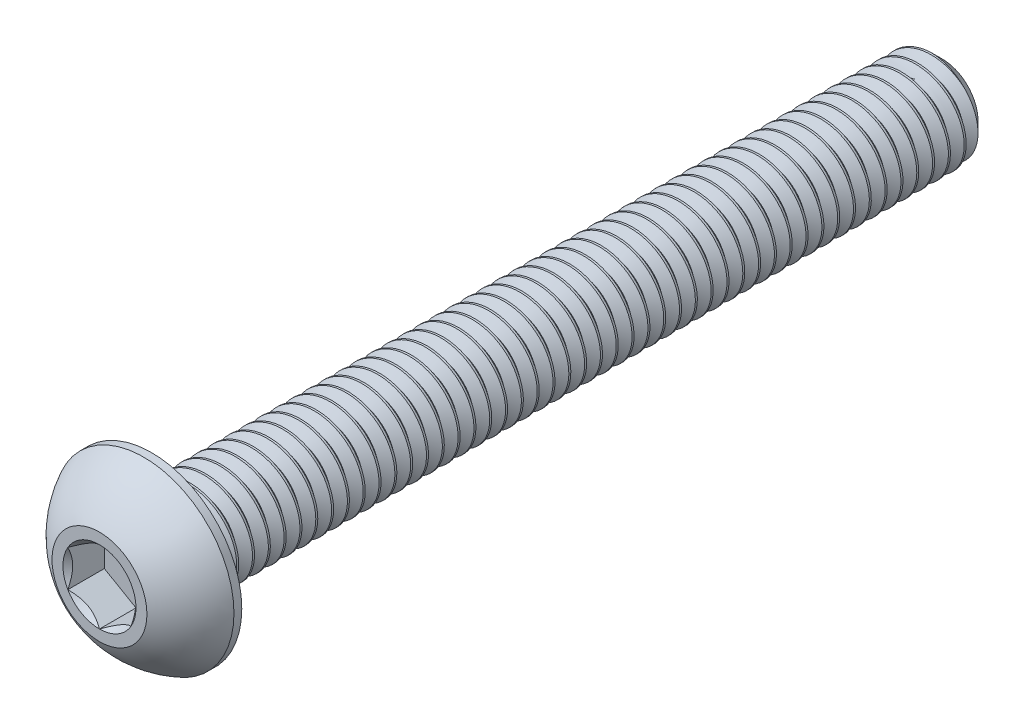
SolidWorks part; units mm, degrees
note: '?' marks a value the reader was unsure of.
ref_plane "Front" through (0, 0, 0) normal (0, 0, 1) x (1, 0, 0)
ref_plane "Top" through (0, 0, 0) normal (0, 1, 0) x (1, 0, 0)
ref_plane "Right" through (0, 0, 0) normal (1, 0, 0) x (0, 0, -1)
sketch "Sketch1" plane through (0, 0, 0) normal (1, 0, 0) x (0, 0, -1)
  line L2 (1.65, 1.5) -> (26.65, 1.5)
  line L3 (26.65, 1.5) -> (26.65, 0)
  line L4 (26.65, 0) -> (1.65, 0)
  line L6 (1.4025, 2.85) -> (1.65, 2.85) construction
  line L7 (26.65, 1.5) -> (26.65, -1.5) construction
  line L8 (0, 0) -> (1.65, 0) construction
  line L9 (1.65, 2.85) -> (1.65, -2.85) construction
  line L11 (1.65, 1.5) -> (1.65, 0)
  line L13 (0, 1) -> (0, -1) construction
  line L14 (0, 1) -> (0, 1.5) construction
  arc A3 (0, 1.5) -> (1.4025, 2.85) centre (2.7948, 0) cw construction
  dimension "D1" = 0.2475
revolve "Revolve1" add sketch "Sketch1" angle 360 mid plane about L4
sketch "Sketch3" plane through (0, 0, -26.65) normal (0, 0, -1) x (-1, 0, 0)
  circle A0 centre (0, 0) radius 1.5
curve "Helix/Spiral1" pitch 0.5 height 25.5 turns 51
chamfer "Chamfer1" distance 0.375 angle 45 1 edges at (0, 1.5, -26.65)
sketch "Sketch7" plane through (0, 0, 0) normal (1, 0, 0) x (0, 0, -1)
  line L6 (1.4025, 2.85) -> (1.65, 2.85) construction
  line L8 (0, 0) -> (1.65, 0) construction
  line L11 (1.65, 2.85) -> (1.65, -2.85) construction
  line L12 (1.4025, 2.85) -> (1.65, 2.85)
  line L13 (0, 0) -> (1.65, 0)
  line L14 (0, 1) -> (0, -1) construction
  line L15 (1.65, 2.85) -> (1.65, 0)
  line L16 (0, 1.5) -> (0, 0)
  arc A2 (1.4025, 2.85) -> (0, 1.5) centre (2.7948, 0) ccw construction
  arc A3 (1.4025, 2.85) -> (0, 1.5) centre (2.7948, 0) ccw
revolve "Revolve2" add sketch "Sketch7" angle 360 mid plane about L13
sketch "Sketch5" plane through (0, 0, 0) normal (0, 0, 1) x (1, 0, 0)
  line L1 (1, -0.5774) -> (1, 0.5774)
  line L2 (1, 0.5774) -> (0, 1.1547)
  line L3 (0, 1.1547) -> (-1, 0.5774)
  line L4 (-1, 0.5774) -> (-1, -0.5774)
  line L5 (-1, -0.5774) -> (0, -1.1547)
  line L6 (0, -1.1547) -> (1, -0.5774)
  circle A0 centre (0, 0) radius 1 construction
extrude "Cut-Extrude2" cut sketch "Sketch5" against normal blind 1.155
sketch "Sketch6" plane through (0, 0, 0) normal (0, 0, 1) x (1, 0, 0)
  circle A0 centre (0, 0) radius 1.1547
extrude "Cut-Extrude3" cut sketch "Sketch6" against normal blind 1.155 draft 45
sketch "Sketch2" plane through (0, 0, 0) normal (1, 0, 0) x (0, 0, -1)
  line L0 (26.275, 1.5) -> (26.7125, 1.5)
  line L1 (26.7125, 1.5) -> (26.525, 1.1752)
  line L2 (26.525, 1.1752) -> (26.4625, 1.1752)
  line L3 (26.4625, 1.1752) -> (26.275, 1.5)
  line L4 (26.3688, 1.3376) -> (26.6188, 1.3376) construction
  dimension "D1" = 60
  dimension "D2" = 0.0625
  dimension "D3" = 0.25
sweep "Cut-Sweep1" cut profiles "Sketch2" path "Helix/Spiral1"
sketch "Sketch10" plane through (0, 0, 0) normal (1, 0, 0) x (0, 0, -1)
  line L0 (26.65, 1.5) -> (26.65, -1.5) construction
  point P0 (25.9, -1.5)
  dimension "D1" = 0.75
ref_axis "Center Axis 1" through (0, 0, -8.1113) along (0, 0, 1)?
ref_plane "Contact Plane 1" through (0, 0, -1.65) normal (0, 0, -1) x (-1, 0, 0)
ref_plane "Contact Plane 2" through (0, 0, 0) normal (0, 0, 1) x (1, 0, 0)
equation "\"D3@Helix/Spiral1\" = \"Lg@Sketch1\" + \"D4@Helix/Spiral1\""
equation "\"D2@Sketch2\" = \"D4@Helix/Spiral1\" * .125"
equation "\"D3@Sketch2\" = \"D4@Helix/Spiral1\" * .5"
equation "\"D1@Chamfer1\" = \"D4@Helix/Spiral1\" * .75"
equation "\"D1@Cut-Extrude2\" = \"Head Ht@Sketch1\" * .7"
equation "\"D1@Sketch1\" = \"Head Ht@Sketch1\" * .15"
equation "\"D1@Sketch10\" = \"D4@Helix/Spiral1\" * 1.5"
equation "\"D1@Cut-Extrude3\" = \"D1@Cut-Extrude2\""
